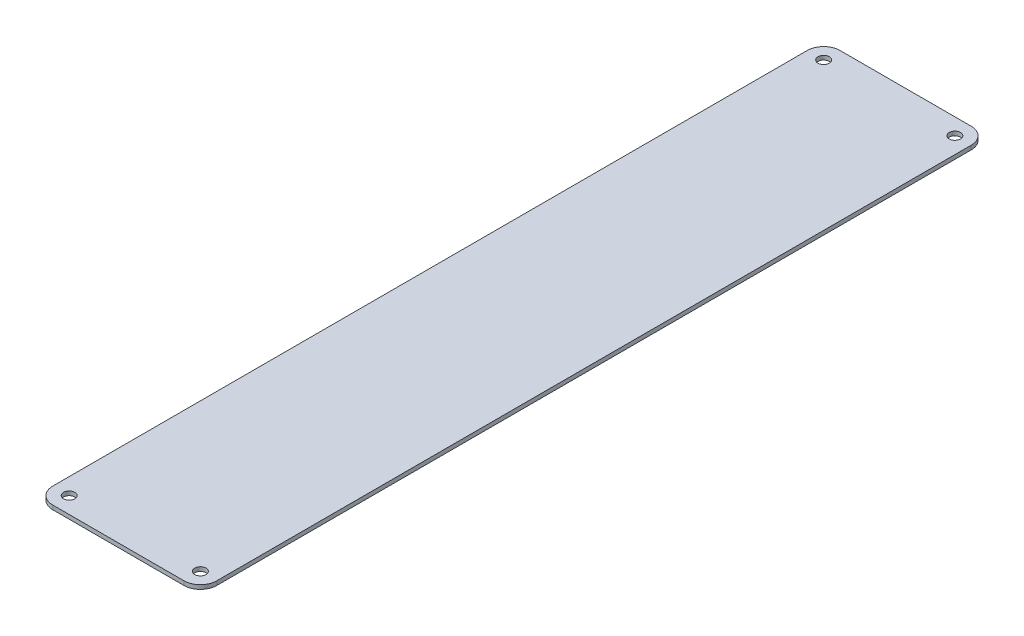
SolidWorks part; units mm, degrees
ref_plane "Front Plane" through (0, 0, 0) normal (0, 0, 1) x (1, 0, 0)
ref_plane "Top Plane" through (0, 0, 0) normal (0, 1, 0) x (1, 0, 0)
ref_plane "Right Plane" through (0, 0, 0) normal (1, 0, 0) x (0, 0, -1)
sketch "Sketch1" plane through (0, 0, 0) normal (0, 1, 0) x (1, 0, 0)
  line L1 (6.35, 0) -> (57.15, 0)
  line L2 (0, 6.35) -> (0, 298.45)
  line L3 (6.35, 304.8) -> (57.15, 304.8)
  line L4 (63.5, 6.35) -> (63.5, 298.45)
  circle A0 centre (57.15, 298.45) radius 2.1828
  circle A1 centre (6.35, 298.45) radius 2.1828
  circle A2 centre (6.35, 6.35) radius 2.1828
  circle A3 centre (57.15, 6.35) radius 2.1828
  arc A4 (6.35, 304.8) -> (0, 298.45) centre (6.35, 298.45) ccw
  arc A5 (6.35, 0) -> (0, 6.35) centre (6.35, 6.35) cw
  arc A6 (63.5, 6.35) -> (57.15, 0) centre (57.15, 6.35) cw
  arc A7 (63.5, 298.45) -> (57.15, 304.8) centre (57.15, 298.45) ccw
  point P13 (0, 0)
  point P16 (0, 304.8)
  point P19 (0, 0)
  point P22 (63.5, 0)
  dimension "D6" = 4.3656
  dimension "D8" = 4.3656
  dimension "D9" = 6.35
  dimension "D10" = 6.35
  dimension "D11" = 6.35
  dimension "D14" = 4.3656
  dimension "D17" = 4.3656
  dimension "D18" = 6.35
  dimension "D1" = 63.5
  dimension "D2" = 304.8
  dimension "D3" = 6.35
  dimension "D4" = 6.35
  dimension "D5" = 6.35
  dimension "D7" = 6.35
  dimension "D12" = 6.35
  dimension "D13" = 6.35
  dimension "D15" = 6.35
  dimension "D16" = 6.35
extrude "Boss-Extrude1" add sketch "Sketch1" along normal mid plane 1.5875
